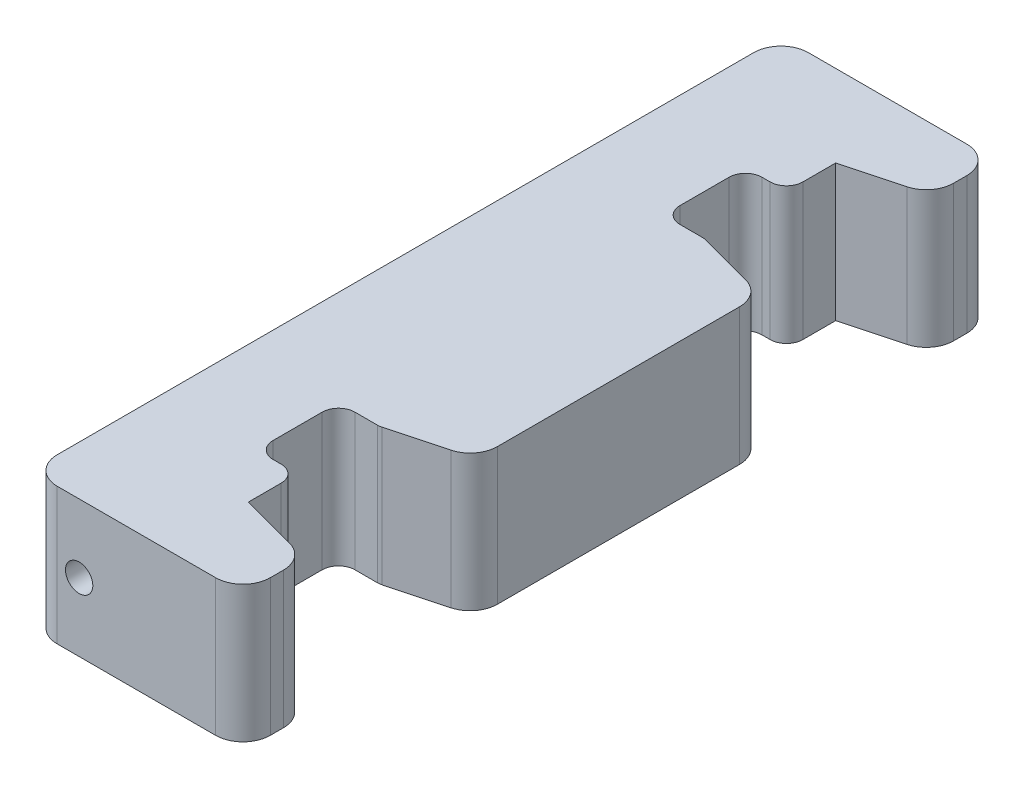
SolidWorks part; units mm, degrees
ref_plane "Front Plane" through (0, 0, 0) normal (0, 0, 1) x (1, 0, 0)
ref_plane "Top Plane" through (0, 0, 0) normal (0, 1, 0) x (1, 0, 0)
ref_plane "Right Plane" through (0, 0, 0) normal (1, 0, 0) x (0, 0, -1)
sketch "Sketch1" plane through (0, 0, 0) normal (0, 1, 0) x (1, 0, 0)
  line L0 (-13.97, 34.925) -> (13.97, -34.925) construction
  line L1 (-13.97, 34.925) -> (13.97, 34.925)
  line L2 (-13.97, 34.925) -> (-13.97, -34.925)
  line L3 (-13.97, -34.925) -> (13.97, -34.925)
  line L4 (13.97, 34.925) -> (13.97, -34.925)
  line L5 (-13.97, -34.925) -> (13.97, 34.925) construction
  line L6 (5.842, 15.113) -> (5.842, -15.113)
  line L7 (13.97, 34.925) -> (5.842, 34.925)
  line L8 (13.97, 34.925) -> (13.97, 15.113)
  line L9 (13.97, 15.113) -> (5.842, 15.113)
  line L10 (5.842, 34.925) -> (5.842, 15.113)
  line L11 (13.97, -34.925) -> (5.842, -34.925)
  line L12 (13.97, -34.925) -> (13.97, -15.113)
  line L13 (13.97, -15.113) -> (5.842, -15.113)
  line L14 (5.842, -34.925) -> (5.842, -15.113)
  line L15 (5.842, 15.113) -> (-1.27, 15.113)
  line L16 (5.842, 15.113) -> (5.842, 27.305)
  line L17 (5.842, 27.305) -> (-1.27, 27.305)
  line L18 (-1.27, 15.113) -> (-1.27, 27.305)
  line L23 (5.842, -15.113) -> (-1.27, -15.113)
  line L24 (5.842, -15.113) -> (5.842, -27.305)
  line L25 (5.842, -27.305) -> (-1.27, -27.305)
  line L26 (-1.27, -15.113) -> (-1.27, -27.305)
  line L28 (-1.27, 15.113) -> (-5.08, 15.113)
  line L29 (-1.27, 15.113) -> (-1.27, 22.733)
  line L30 (-1.27, 22.733) -> (-5.08, 22.733)
  line L31 (-5.08, 15.113) -> (-5.08, 22.733)
  line L32 (-1.27, -15.113) -> (-5.08, -15.113)
  line L33 (-1.27, -15.113) -> (-1.27, -22.733)
  line L34 (-1.27, -22.733) -> (-5.08, -22.733)
  line L35 (-5.08, -15.113) -> (-5.08, -22.733)
  point P4 (0, 0)
  dimension "D1" = 27.94
  dimension "D2" = 69.85
  dimension "D3" = 19.812
  dimension "D4" = 8.128
  dimension "D5" = 19.812
  dimension "D6" = 8.128
  dimension "D7" = 12.7
  dimension "D8" = 7.62
  dimension "D9" = 7.62
  dimension "D10" = 12.7
  dimension "D11" = 7.62
  dimension "D12" = 3.81
  dimension "D13" = 7.62
  dimension "D14" = 3.81
extrude "Boss-Extrude1" add sketch "Sketch1" along normal blind 12.7 contours L35 L32 L23 L6 L15 L28 L31 L30 L18 L17 L10 L1 L2 L3 L14 L25 L26 L34 region at (-5.0644, 0, 0)
sketch "Sketch2" plane through (0, 12.7, 0) normal (0, 1, 0) x (1, 0, 0)
  line L0 (-1.27, 27.305) -> (5.842, 29.2107)
  line L1 (5.842, 34.925) -> (5.842, 27.305) construction
  line L2 (5.842, 27.305) -> (-1.27, 27.305) construction
  line L3 (-1.27, -27.305) -> (5.842, -29.2107)
  line L4 (5.842, -34.925) -> (5.842, -27.305) construction
  line L5 (5.842, -27.305) -> (-1.27, -27.305) construction
  line L6 (-1.27, -15.113) -> (5.842, -13.2073)
  line L7 (5.842, -15.113) -> (-5.08, -15.113) construction
  line L8 (5.842, 15.113) -> (5.842, -15.113) construction
  line L9 (-1.27, 15.113) -> (5.842, 13.2073)
  line L10 (5.842, 15.113) -> (-5.08, 15.113) construction
  line L11 (-1.27, 27.305) -> (5.842, 27.305)
  line L12 (5.842, 27.305) -> (5.842, 29.2107)
  line L13 (-1.27, 15.113) -> (5.842, 15.113)
  line L14 (5.842, 15.113) -> (5.842, 13.2073)
  line L15 (-1.27, -15.113) -> (5.842, -15.113)
  line L16 (5.842, -13.2073) -> (5.842, -15.113)
  line L17 (-1.27, -27.305) -> (5.842, -27.305)
  line L18 (5.842, -27.305) -> (5.842, -29.2107)
  dimension "D1" = 15
  dimension "D2" = 15
  dimension "D3" = 15
  dimension "D4" = 15
extrude "Cut-Extrude1" cut sketch "Sketch2" against normal through all
fillet "Fillet4" radius 1.524 8 edges at (-1.27, 6.35, -15.113) (-1.27, 6.35, 15.113) (-1.27, 6.35, 22.733) (-5.08, 6.35, 22.733) (-5.08, 6.35, 15.113) (-5.08, 6.35, -15.113) (-5.08, 6.35, -22.733) (-1.27, 6.35, -22.733)
fillet "Fillet5" radius 2.54 8 edges at (-13.97, 6.35, 34.925) (-13.97, 6.35, -34.925) (5.842, 6.35, -34.925) (5.842, 6.35, -29.2107) (5.842, 6.35, -13.2073) (5.842, 6.35, 13.2073) (5.842, 6.35, 34.925) (5.842, 6.35, 29.2107)
sketch "Sketch3" plane through (0, 0, 34.925) normal (0, 0, 1) x (1, 0, 0)
  line L0 (-11.43, 0) -> (3.302, 0) construction
  circle A0 centre (-9.392, 6.35) radius 1.27
  dimension "D1" = 2.54
  dimension "D2" = 6.35
extrude "Cut-Extrude2" cut sketch "Sketch3" against normal through all
